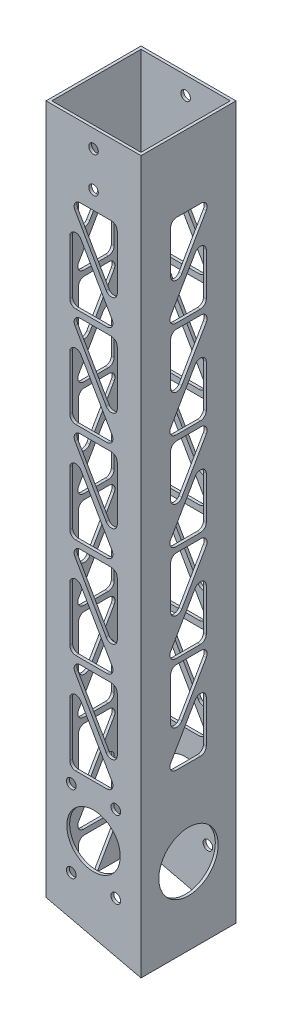
SolidWorks part; units mm, degrees
material "6061 Alloy"
ref_plane "Front Plane" through (0, 0, 0) normal (0, 0, 1) x (1, 0, 0)
ref_plane "Top Plane" through (0, 0, 0) normal (0, 1, 0) x (1, 0, 0)
ref_plane "Right Plane" through (0, 0, 0) normal (1, 0, 0) x (0, 0, -1)
sketch "Sketch1" plane through (0, 0, 0) normal (0, 1, 0) x (1, 0, 0)
  line L1 (25.4, 25.4) -> (-25.4, 25.4)
  line L2 (25.4, 25.4) -> (25.4, -25.4)
  line L3 (25.4, -25.4) -> (-25.4, -25.4)
  line L4 (-25.4, 25.4) -> (-25.4, -25.4)
  line L5 (25.4, 25.4) -> (-25.4, -25.4) construction
  line L6 (25.4, -25.4) -> (-25.4, 25.4) construction
  point P0 (0, 0)
  dimension "D1" = 50.8
extrude "Extrude-Thin1" add sketch "Sketch1" along normal blind 381 thin thin type one direction reverse wall 1.524
sketch "Sketch2" plane through (0, 0, 0) normal (0, 0, 1) x (1, 0, 0)
  line L0 (-36.2563, 68.2625) -> (38.5702, 68.2625) construction
  line L1 (-25.4, 0) -> (25.4, 0) construction
  line L2 (-25.4, 50.8) -> (25.4, 50.8) construction
  line L6 (25.4, 381) -> (25.4, 0) construction
  line L7 (-25.4, 381) -> (-25.4, 0) construction
  line L8 (-11.9062, 30.1778) -> (11.9063, 30.1778) construction
  line L9 (-11.9062, 71.4222) -> (11.9063, 71.4222) construction
  circle A0 centre (0, 50.8) radius 14.3002
  circle A1 centre (0, 50.8) radius 23.8125 construction
  circle A2 centre (-11.9062, 30.1778) radius 2.5908
  circle A3 centre (11.9063, 30.1778) radius 2.5908
  circle A4 centre (11.9063, 71.4222) radius 2.5908
  circle A5 centre (-11.9062, 71.4222) radius 2.5908
  point P11 (0, 50.8)
  dimension "D1" = 28.6004
  dimension "D3" = 17.4625
  dimension "D4" = 47.625
  dimension "D6" = 5.1816
  dimension "D2" = 50.8
  dimension "D5" = 60
extrude "Cut-Extrude1" cut sketch "Sketch2" along normal through all both and the other way through all
sketch "Sketch3" plane through (25.4, 0, 0) normal (1, 0, 0) x (0, 0, -1)
  line L0 (-25.4, 50.8) -> (25.4, 50.8) construction
  line L1 (-25.4, 65.1002) -> (-25.4, 36.4998) construction
  line L3 (25.4, 381) -> (25.4, 0) construction
  circle A0 centre (0, 41.275) radius 15.875
  point P9 (0, 50.8)
  dimension "D1" = 31.75
  dimension "D2" = 9.525
extrude "Cut-Extrude2" cut sketch "Sketch3" against normal up to surface (1.524 mm away) up to face at (23.876, 190.5, 0)
sketch "Sketch4" plane through (0, 0, 25.4) normal (0, 0, 1) x (1, 0, 0)
  line L0 (-25.4, 381) -> (25.4, 381) construction
  circle A0 centre (0, 371.475) radius 2.54
  circle A1 centre (0, 352.425) radius 2.54
  dimension "D1" = 5.08
  dimension "D2" = 9.525
  dimension "D3" = 28.575
hole_wizard "#10 Clearance Hole1" positions "Sketch5" profile "Sketch6" hole size "#10" standard "ANSI Inch" end condition through all
sketch "Sketch5" plane through (0, 0, 25.4) normal (0, 0, 1) x (1, 0, 0)
  point P0 (0, 352.425)
  point P3 (0, 371.475)
sketch "Sketch6" plane through (0, 352.425, 25.4) normal (1, 0, 0) x (0, -1, 0)
  line L0 (0, 0) -> (0, 50.8)
  line L1 (0, 50.8) -> (2.5527, 50.8)
  line L2 (2.5527, 50.8) -> (2.5527, 0)
  line L5 (2.5527, 0) -> (0, 0)
  line L11 (0, -6.35) -> (0, 107.95) construction
  dimension "Thru Hole Dia." = 5.1054
  dimension "Thru Hole Depth" = 50.8
sketch "Sketch7" plane through (0, 0, 25.4) normal (0, 0, 1) x (1, 0, 0)
  line L0 (-12.7, 381) -> (-12.7, 0) construction
  line L1 (12.7, 381) -> (12.7, 0) construction
  line L2 (-12.7, 0) -> (-25.4, 0) construction
  line L3 (-25.4, 0) -> (25.4, 0) construction
  line L4 (-25.4, 381) -> (-25.4, 0) construction
  line L5 (12.7, 0) -> (25.4, 0) construction
  line L6 (-25.4, 381) -> (25.4, 381) construction
  line L7 (-12.7, 342.9) -> (12.7, 342.9) construction
  line L8 (-12.7, 79.375) -> (12.7, 79.375) construction
  line L9 (-7.2007, 342.9) -> (9.525, 342.9)
  line L10 (12.7, 339.725) -> (12.7, 310.7552)
  line L11 (6.7754, 309.1677) -> (-9.9504, 338.1375)
  line L12 (-9.525, 292.5559) -> (7.2007, 292.5559)
  line L13 (-12.7, 295.7309) -> (-12.7, 324.7007)
  line L14 (-6.7754, 326.2882) -> (9.9504, 297.3184)
  line L15 (-0.1024, 314.7303) -> (2.6473, 316.3178) construction
  line L16 (-7.2007, 289.3809) -> (9.525, 289.3809)
  line L17 (12.7, 286.2059) -> (12.7, 257.2361)
  line L18 (6.7754, 255.6486) -> (-9.9504, 284.6184)
  line L19 (-12.7, 242.2118) -> (-12.7, 271.1816)
  line L20 (-9.525, 239.0368) -> (7.2007, 239.0368)
  line L21 (-6.7754, 272.7691) -> (9.9504, 243.7993)
  line L34 (-7.2007, 342.9) -> (-7.2007, 289.3809) construction
  line L35 (-7.2007, 235.8618) -> (9.525, 235.8618)
  line L36 (12.7, 232.6868) -> (12.7, 203.717)
  line L37 (6.7754, 202.1295) -> (-9.9504, 231.0993)
  line L38 (-12.7, 188.6927) -> (-12.7, 217.6626)
  line L39 (-9.525, 185.5177) -> (7.2007, 185.5177)
  line L40 (-6.7754, 219.2501) -> (9.9504, 190.2802)
  line L41 (-7.2007, 182.3427) -> (9.525, 182.3427)
  line L42 (12.7, 179.1677) -> (12.7, 150.1979)
  line L43 (6.7754, 148.6104) -> (-9.9504, 177.5802)
  line L44 (-12.7, 135.1736) -> (-12.7, 164.1435)
  line L45 (-9.525, 131.9986) -> (7.2007, 131.9986)
  line L46 (-6.7754, 165.731) -> (9.9504, 136.7611)
  line L47 (-7.2007, 128.8236) -> (9.525, 128.8236)
  line L48 (12.7, 125.6486) -> (12.7, 96.6788)
  line L49 (6.7754, 95.0913) -> (-9.9504, 124.0611)
  line L50 (-12.7, 81.6545) -> (-12.7, 110.6244)
  line L51 (-9.525, 78.4795) -> (7.2007, 78.4795)
  line L52 (-6.7754, 112.2119) -> (9.9504, 83.242)
  arc A0 (-9.9504, 338.1375) -> (-7.2007, 342.9) centre (-7.2007, 339.725) cw
  arc A1 (9.525, 342.9) -> (12.7, 339.725) centre (9.525, 339.725) cw
  arc A2 (12.7, 310.7552) -> (6.7754, 309.1677) centre (9.525, 310.7552) cw
  arc A3 (9.9504, 297.3184) -> (7.2007, 292.5559) centre (7.2007, 295.7309) cw
  arc A4 (-12.7, 324.7007) -> (-6.7754, 326.2882) centre (-9.525, 324.7007) cw
  arc A5 (-12.7, 295.7309) -> (-9.525, 292.5559) centre (-9.525, 295.7309) ccw
  arc A6 (12.7, 257.2361) -> (6.7754, 255.6486) centre (9.525, 257.2361) cw
  arc A7 (-9.9504, 284.6184) -> (-7.2007, 289.3809) centre (-7.2007, 286.2059) cw
  arc A8 (9.525, 289.3809) -> (12.7, 286.2059) centre (9.525, 286.2059) cw
  arc A9 (-12.7, 271.1816) -> (-6.7754, 272.7691) centre (-9.525, 271.1816) cw
  arc A10 (-12.7, 242.2118) -> (-9.525, 239.0368) centre (-9.525, 242.2118) ccw
  arc A11 (9.9504, 243.7993) -> (7.2007, 239.0368) centre (7.2007, 242.2118) cw
  arc A12 (12.7, 203.717) -> (6.7754, 202.1295) centre (9.525, 203.717) cw
  arc A13 (-9.9504, 231.0993) -> (-7.2007, 235.8618) centre (-7.2007, 232.6868) cw
  arc A14 (9.525, 235.8618) -> (12.7, 232.6868) centre (9.525, 232.6868) cw
  arc A15 (-12.7, 217.6626) -> (-6.7754, 219.2501) centre (-9.525, 217.6626) cw
  arc A16 (-12.7, 188.6927) -> (-9.525, 185.5177) centre (-9.525, 188.6927) ccw
  arc A17 (9.9504, 190.2802) -> (7.2007, 185.5177) centre (7.2007, 188.6927) cw
  arc A18 (12.7, 150.1979) -> (6.7754, 148.6104) centre (9.525, 150.1979) cw
  arc A19 (-9.9504, 177.5802) -> (-7.2007, 182.3427) centre (-7.2007, 179.1677) cw
  arc A20 (9.525, 182.3427) -> (12.7, 179.1677) centre (9.525, 179.1677) cw
  arc A21 (-12.7, 164.1435) -> (-6.7754, 165.731) centre (-9.525, 164.1435) cw
  arc A22 (-12.7, 135.1736) -> (-9.525, 131.9986) centre (-9.525, 135.1736) ccw
  arc A23 (9.9504, 136.7611) -> (7.2007, 131.9986) centre (7.2007, 135.1736) cw
  arc A24 (12.7, 96.6788) -> (6.7754, 95.0913) centre (9.525, 96.6788) cw
  arc A25 (-9.9504, 124.0611) -> (-7.2007, 128.8236) centre (-7.2007, 125.6486) cw
  arc A26 (9.525, 128.8236) -> (12.7, 125.6486) centre (9.525, 125.6486) cw
  arc A27 (-12.7, 110.6244) -> (-6.7754, 112.2119) centre (-9.525, 110.6244) cw
  arc A28 (-12.7, 81.6545) -> (-9.525, 78.4795) centre (-9.525, 81.6545) ccw
  arc A29 (9.9504, 83.242) -> (7.2007, 78.4795) centre (7.2007, 81.6545) cw
  point P31 (12.7, 298.9059)
  point P34 (12.7, 292.5559)
  point P37 (-12.7, 336.55)
  point P40 (-12.7, 292.5559)
  dimension "D5" = 3.175
  dimension "D1" = 12.7
  dimension "D2" = 38.1
  dimension "D3" = 79.375
  dimension "D4" = 30
  dimension "D7" = 3.175
  dimension "D8" = 3.175
  dimension "D6" = 5
extrude "Cut-Extrude3" cut sketch "Sketch7" against normal through all
sketch "Sketch8" plane through (-25.4, 0, 0) normal (-1, 0, 0) x (0, 0, 1)
  line L0 (-12.2746, 342.9) -> (9.525, 342.9) construction
  line L1 (-6.7754, 342.9) -> (6.35, 342.9)
  line L2 (9.525, 339.725) -> (9.525, 316.9912)
  line L3 (3.6004, 315.4037) -> (-9.525, 338.1375)
  line L4 (-6.35, 294.0294) -> (6.7754, 294.0294)
  line L5 (-9.525, 297.2044) -> (-9.525, 319.9382)
  line L6 (-3.6004, 321.5257) -> (9.525, 298.7919)
  line L7 (4.3689, 307.7225) -> (7.1185, 309.31) construction
  line L8 (-9.525, 381) -> (-9.525, 0) construction
  line L9 (-25.4, 0) -> (25.4, 0) construction
  line L10 (9.525, 0) -> (9.525, 381) construction
  line L11 (-25.4, 381) -> (25.4, 381) construction
  line L12 (-9.525, 392.3126) -> (-25.4, 392.3126) construction
  line L13 (-25.4, 381) -> (-25.4, 0) construction
  line L14 (9.525, 392.3126) -> (25.4, 392.3126) construction
  line L15 (25.4, 381) -> (25.4, 0) construction
  line L16 (-6.35, 242.2379) -> (6.7754, 242.2379)
  line L17 (-9.525, 245.4129) -> (-9.525, 268.1467)
  line L18 (-3.6004, 269.7342) -> (9.525, 247.0004)
  line L19 (9.525, 287.9334) -> (9.525, 265.1996)
  line L20 (3.6004, 263.6121) -> (-9.525, 286.3459)
  line L21 (-6.7754, 291.1084) -> (6.35, 291.1084)
  line L22 (-6.35, 190.4463) -> (6.7754, 190.4463)
  line L23 (-9.525, 193.6213) -> (-9.525, 216.3551)
  line L24 (-3.6004, 217.9426) -> (9.525, 195.2088)
  line L25 (9.525, 236.1419) -> (9.525, 213.4081)
  line L26 (3.6004, 211.8206) -> (-9.525, 234.5544)
  line L27 (-6.7754, 239.3169) -> (6.35, 239.3169)
  line L28 (-6.35, 138.6547) -> (6.7754, 138.6547)
  line L29 (-9.525, 141.8297) -> (-9.525, 164.5635)
  line L30 (-3.6004, 166.151) -> (9.525, 143.4172)
  line L31 (9.525, 184.3503) -> (9.525, 161.6165)
  line L32 (3.6004, 160.029) -> (-9.525, 182.7628)
  line L33 (-6.7754, 187.5253) -> (6.35, 187.5253)
  line L34 (-25.4, 87.3125) -> (25.4, 87.3125) construction
  line L35 (-6.35, 86.8632) -> (6.7754, 86.8632)
  line L36 (-9.525, 90.0382) -> (-9.525, 112.772)
  line L37 (-3.6004, 114.3595) -> (9.525, 91.6257)
  line L38 (9.525, 132.5587) -> (9.525, 109.8249)
  line L39 (3.6004, 108.2374) -> (-9.525, 130.9712)
  line L40 (-6.7754, 135.7337) -> (6.35, 135.7337)
  line L41 (-6.35, 35.0716) -> (6.7754, 35.0716)
  line L42 (-9.525, 38.2466) -> (-9.525, 60.9804)
  line L43 (-3.6004, 62.5679) -> (9.525, 39.8341)
  line L44 (9.525, 80.7672) -> (9.525, 58.0334)
  line L45 (3.6004, 56.4459) -> (-9.525, 79.1797)
  line L46 (-6.7754, 83.9422) -> (6.35, 83.9422)
  line L50 (9.525, 28.9756) -> (9.525, 6.2418)
  line L51 (3.6004, 4.6543) -> (-9.525, 27.3881)
  line L52 (-6.7754, 32.1506) -> (6.35, 32.1506)
  line L53 (-6.35, -16.7199) -> (6.7754, -16.7199) [skipped]
  line L54 (-3.6004, 10.7764) -> (9.525, -11.9574) [skipped]
  line L55 (-9.525, -13.5449) -> (-9.525, 9.1889) [skipped]
  arc A0 (-9.525, 338.1375) -> (-6.7754, 342.9) centre (-6.7754, 339.725) cw
  arc A1 (6.35, 342.9) -> (9.525, 339.725) centre (6.35, 339.725) cw
  arc A2 (9.525, 316.9912) -> (3.6004, 315.4037) centre (6.35, 316.9912) cw
  arc A3 (9.525, 298.7919) -> (6.7754, 294.0294) centre (6.7754, 297.2044) cw
  arc A4 (-9.525, 319.9382) -> (-3.6004, 321.5257) centre (-6.35, 319.9382) cw
  arc A5 (-9.525, 297.2044) -> (-6.35, 294.0294) centre (-6.35, 297.2044) ccw
  arc A6 (-9.525, 245.4129) -> (-6.35, 242.2379) centre (-6.35, 245.4129) ccw
  arc A7 (-9.525, 268.1467) -> (-3.6004, 269.7342) centre (-6.35, 268.1467) cw
  arc A8 (9.525, 247.0004) -> (6.7754, 242.2379) centre (6.7754, 245.4129) cw
  arc A9 (9.525, 265.1996) -> (3.6004, 263.6121) centre (6.35, 265.1996) cw
  arc A10 (6.35, 291.1084) -> (9.525, 287.9334) centre (6.35, 287.9334) cw
  arc A11 (-9.525, 286.3459) -> (-6.7754, 291.1084) centre (-6.7754, 287.9334) cw
  arc A12 (-9.525, 193.6213) -> (-6.35, 190.4463) centre (-6.35, 193.6213) ccw
  arc A13 (-9.525, 216.3551) -> (-3.6004, 217.9426) centre (-6.35, 216.3551) cw
  arc A14 (9.525, 195.2088) -> (6.7754, 190.4463) centre (6.7754, 193.6213) cw
  arc A15 (9.525, 213.4081) -> (3.6004, 211.8206) centre (6.35, 213.4081) cw
  arc A16 (6.35, 239.3169) -> (9.525, 236.1419) centre (6.35, 236.1419) cw
  arc A17 (-9.525, 234.5544) -> (-6.7754, 239.3169) centre (-6.7754, 236.1419) cw
  arc A18 (-9.525, 141.8297) -> (-6.35, 138.6547) centre (-6.35, 141.8297) ccw
  arc A19 (-9.525, 164.5635) -> (-3.6004, 166.151) centre (-6.35, 164.5635) cw
  arc A20 (9.525, 143.4172) -> (6.7754, 138.6547) centre (6.7754, 141.8297) cw
  arc A21 (9.525, 161.6165) -> (3.6004, 160.029) centre (6.35, 161.6165) cw
  arc A22 (6.35, 187.5253) -> (9.525, 184.3503) centre (6.35, 184.3503) cw
  arc A23 (-9.525, 182.7628) -> (-6.7754, 187.5253) centre (-6.7754, 184.3503) cw
  arc A24 (-9.525, 90.0382) -> (-6.35, 86.8632) centre (-6.35, 90.0382) ccw
  arc A25 (-9.525, 112.772) -> (-3.6004, 114.3595) centre (-6.35, 112.772) cw
  arc A26 (9.525, 91.6257) -> (6.7754, 86.8632) centre (6.7754, 90.0382) cw
  arc A27 (9.525, 109.8249) -> (3.6004, 108.2374) centre (6.35, 109.8249) cw
  arc A28 (6.35, 135.7337) -> (9.525, 132.5587) centre (6.35, 132.5587) cw
  arc A29 (-9.525, 130.9712) -> (-6.7754, 135.7337) centre (-6.7754, 132.5587) cw
  arc A30 (-9.525, 38.2466) -> (-6.35, 35.0716) centre (-6.35, 38.2466) ccw
  arc A31 (-9.525, 60.9804) -> (-3.6004, 62.5679) centre (-6.35, 60.9804) cw
  arc A32 (9.525, 39.8341) -> (6.7754, 35.0716) centre (6.7754, 38.2466) cw
  arc A33 (9.525, 58.0334) -> (3.6004, 56.4459) centre (6.35, 58.0334) cw
  arc A34 (6.35, 83.9422) -> (9.525, 80.7672) centre (6.35, 80.7672) cw
  arc A35 (-9.525, 79.1797) -> (-6.7754, 83.9422) centre (-6.7754, 80.7672) cw
  arc A39 (9.525, 6.2418) -> (3.6004, 4.6543) centre (6.35, 6.2418) cw
  arc A40 (6.35, 32.1506) -> (9.525, 28.9756) centre (6.35, 28.9756) cw
  arc A41 (-9.525, 27.3881) -> (-6.7754, 32.1506) centre (-6.7754, 28.9756) cw
  arc A42 (9.525, -11.9574) -> (6.7754, -16.7199) centre (6.7754, -13.5449) cw [skipped]
  arc A43 (-9.525, 9.1889) -> (-3.6004, 10.7764) centre (-6.35, 9.1889) cw [skipped]
  arc A44 (-9.525, -13.5449) -> (-6.35, -16.7199) centre (-6.35, -13.5449) ccw [skipped]
  point P150 (7.1718, 3.175)
  dimension "D2" = 3.175
  dimension "D1" = 30
  dimension "D3" = 38.1
  dimension "D4" = 15.875
  dimension "D5" = 3.175
  dimension "D7" = 3.175
  dimension "D8" = 87.3125
  dimension "D6" = 7
extrude "Cut-Extrude4" cut sketch "Sketch8" against normal through all contours A14 L24 A13 L23 A12 L22 | A17 L26 A15 L25 A16 L27 | A8 L18 A7 L17 A6 L16 | A11 L20 A9 L19 A10 L21 | L5 A5 L4 A3 L6 A4 | A2 L2 A1 L1 A0 L3 | A23 L32 A21 L31 A22 L33 | A20 L30 A19 L29 A18 L28 | A29 L39 A27 L38 A28 L40 | A26 L37 A25 L36 A24 L35 region at (-25.4, 331.265, 2.0868) region at (-25.4, 305.6645, -2.0868) region at (-25.4, 253.8729, -2.0868) region at (-25.4, 279.4734, 2.0868) region at (-25.4, 202.0813, -2.0868) region at (-25.4, 227.6819, 2.0868) region at (-25.4, 150.2898, -2.0868) region at (-25.4, 175.8903, 2.0868) region at (-25.4, 98.4982, -2.0868) region at (-25.4, 124.0987, 2.0868)
extrude "Cut-Extrude5" cut sketch "Sketch8<4>" against normal up to next contours A41 L51 A39 L50 A40 L52 | A32 L43 A31 L42 A30 L41 | A35 L45 A33 L44 A34 L46 region at (-25.4, 46.7066, -2.0868) region at (-25.4, 72.3072, 2.0868) region at (-25.4, 20.5156, 2.0868)
sketch "Sketch8<4>" plane through (-25.4, 0, 0) normal (-1, 0, 0) x (0, 0, 1) same geometry as "Sketch8"
sketch "Sketch9" plane through (0, 0, -25.4) normal (0, 0, -1) x (-1, 0, 0)
  line L1 (25.4, 381) -> (25.4, 0) construction
  line L2 (25.4, 11.9341) -> (25.4, 0)
  line L3 (25.4, 0) -> (-25.4, 0)
  line L4 (25.4, 11.9341) -> (21.0563, 0) construction
  line L7 (-25.4, 381) -> (-25.4, 0) construction
  line L8 (-25.4, 0) -> (25.4, 11.9341)
  point P5 (-25.4, 0.7445)
  dimension "D1" = 20
  dimension "D2" = 12.7
extrude "Cut-Extrude6" cut sketch "Sketch9" against normal through all
